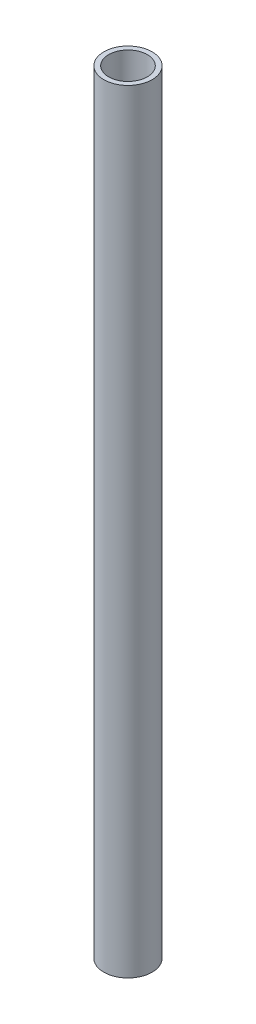
SolidWorks part; units mm, degrees
ref_plane "Front Plane" through (0, 0, 0) normal (0, 0, 1) x (1, 0, 0)
ref_plane "Top Plane" through (0, 0, 0) normal (0, 1, 0) x (1, 0, 0)
ref_plane "Right Plane" through (0, 0, 0) normal (1, 0, 0) x (0, 0, -1)
sketch "Sketch1" plane through (0, 0, 0) normal (0, 1, 0) x (1, 0, 0)
  circle A0 centre (0, 0) radius 3.175
  circle A1 centre (0, 0) radius 2.54
  dimension "D1" = 6.35
  dimension "D2" = 5.08
extrude "Boss-Extrude1" add sketch "Sketch1" along normal blind 101.6
